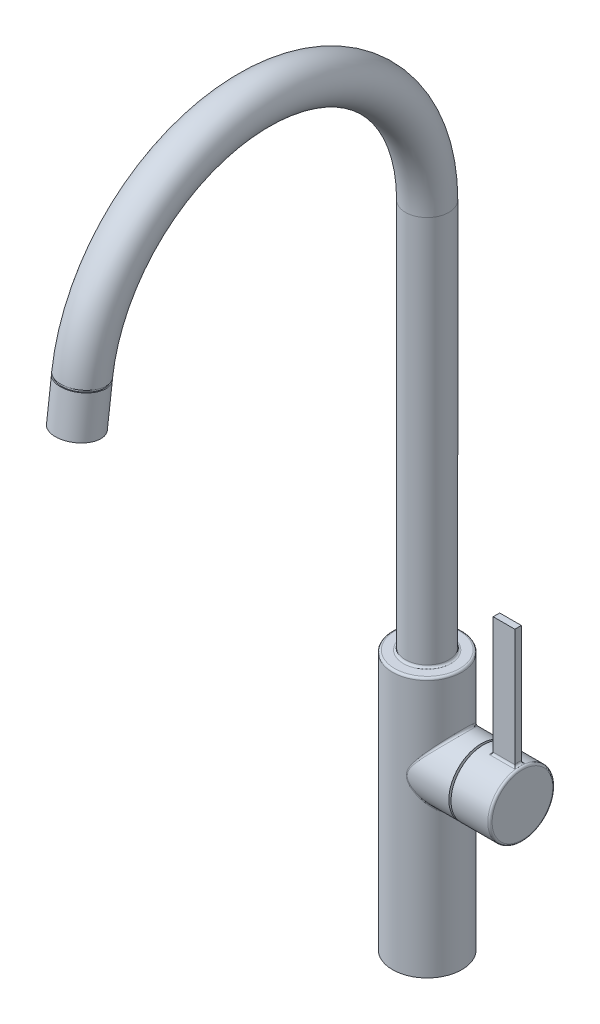
SolidWorks part; units mm, degrees
ref_plane "Alzado" through (0, 0, 0) normal (0, 0, 1) x (1, 0, 0)
ref_plane "Planta" through (0, 0, 0) normal (0, 1, 0) x (1, 0, 0)
ref_plane "Vista lateral" through (0, 0, 0) normal (1, 0, 0) x (0, 0, -1)
sketch "Sketch 1" plane through (0, 0, 0) normal (0, 1, 0) x (1, 0, 0)
  circle A0 centre (0, 0) radius 16
  dimension "D1" = 32
extrude "Extrusion 1" add sketch "Sketch 1" along normal blind 120
sketch "Sketch 2" plane through (0, 120, 0) normal (0, 1, 0) x (1, 0, 0)
  circle A0 centre (0, 0) radius 10
  circle A1 centre (0, 0) radius 9
  dimension "D1" = 20
  dimension "D2" = 18
sketch "Sketch 3" plane through (0, 0, 0) normal (1, 0, 0) x (0, 0, -1)
  line L0 (0, 300) -> (0, 120)
  line L2 (10, 120) -> (-10, 120) construction
  line L3 (-159.4037, 309.7495) -> (-161.8411, 289.8986)
  line L4 (-16, 0) -> (16, 0) construction
  arc A0 (0, 300) -> (-159.4037, 309.7495) centre (-80, 300) ccw
  dimension "D2" = 80
  dimension "D1" = 180
  dimension "D3" = 20
  dimension "D4" = 83
sweep "Swept Boss/Base 1" add profiles "Sketch 2" path "Sketch 3"
ref_plane "Plane 1" through (0, 285.8675, -35.1001) normal (0, -0.9925, 0.1219) x (-1, 0, 0)
sketch "Sketch 4" plane through (0, 285.8675, -35.1001) normal (0, -0.9925, 0.1219) x (-1, 0, 0)
  circle A0 centre (0, -195.9645) radius 9.5
  circle A2 centre (0, -195.9645) radius 10
  dimension "D1" = 19
extrude "Extruded Cut 1" cut sketch "Sketch 4" along normal blind 1
fillet "Fillet 1" radius 1 1 edges at (0, 120, 16)
ref_plane "Plane1" through (5, 0, 0) normal (1, 0, 0) x (0, 0, -1)
sketch "Sketch5" plane through (5, 0, 0) normal (1, 0, 0) x (0, 0, -1)
  line L0 (0, 120) -> (0, 0) construction
  line L1 (15, 120) -> (-15, 120) construction
  line L2 (-16, 0) -> (16, 0) construction
  circle A0 centre (0, 80) radius 15
  dimension "D1" = 30
  dimension "D2" = 80
extrude "Boss-Extrude1" add sketch "Sketch5" along normal blind 20
sketch "Sketch6" plane through (25, 0, 0) normal (1, 0, 0) x (0, 0, -1)
  circle A2 centre (0, 80) radius 13
  circle A3 centre (0, 80) radius 13
  dimension "D1" = 2
extrude "Boss-Extrude2" add sketch "Sketch6" along normal blind 1
sketch "Sketch7" plane through (26, 0, 0) normal (1, 0, 0) x (0, 0, -1)
  circle A2 centre (0, 80) radius 15
  circle A3 centre (0, 80) radius 15
  dimension "D1" = 2
extrude "Boss-Extrude3" add sketch "Sketch7" along normal blind 18
ref_plane "Plane2" through (0, 85, 0) normal (0, 1, 0) x (1, 0, 0)
sketch "Sketch8" plane through (0, 85, 0) normal (0, 1, 0) x (1, 0, 0)
  line L0 (44, 0) -> (16, 0) construction
  line L1 (44, -15) -> (44, 15) construction
  line L3 (42, 1.5) -> (32, 1.5)
  line L4 (42, 1.5) -> (42, -1.5)
  line L5 (42, -1.5) -> (32, -1.5)
  line L6 (32, 1.5) -> (32, -1.5)
  arc A0 (5.5678, -15) -> (5.5678, 15) centre (0, 0) ccw construction
  dimension "D1" = 3
  dimension "D2" = 1.5
  dimension "D3" = 10
  dimension "D4" = 2
extrude "Boss-Extrude4" add sketch "Sketch8" along normal blind 65
fillet "Fillet1" radius 1 7 edges at (44, 80, -15) (5.7517, 81.4429, -14.9304) (0, 120, 10) (32, 95, 0) (42, 95, 0) (37, 94.9248, -1.5) (37, 94.9248, 1.5)
